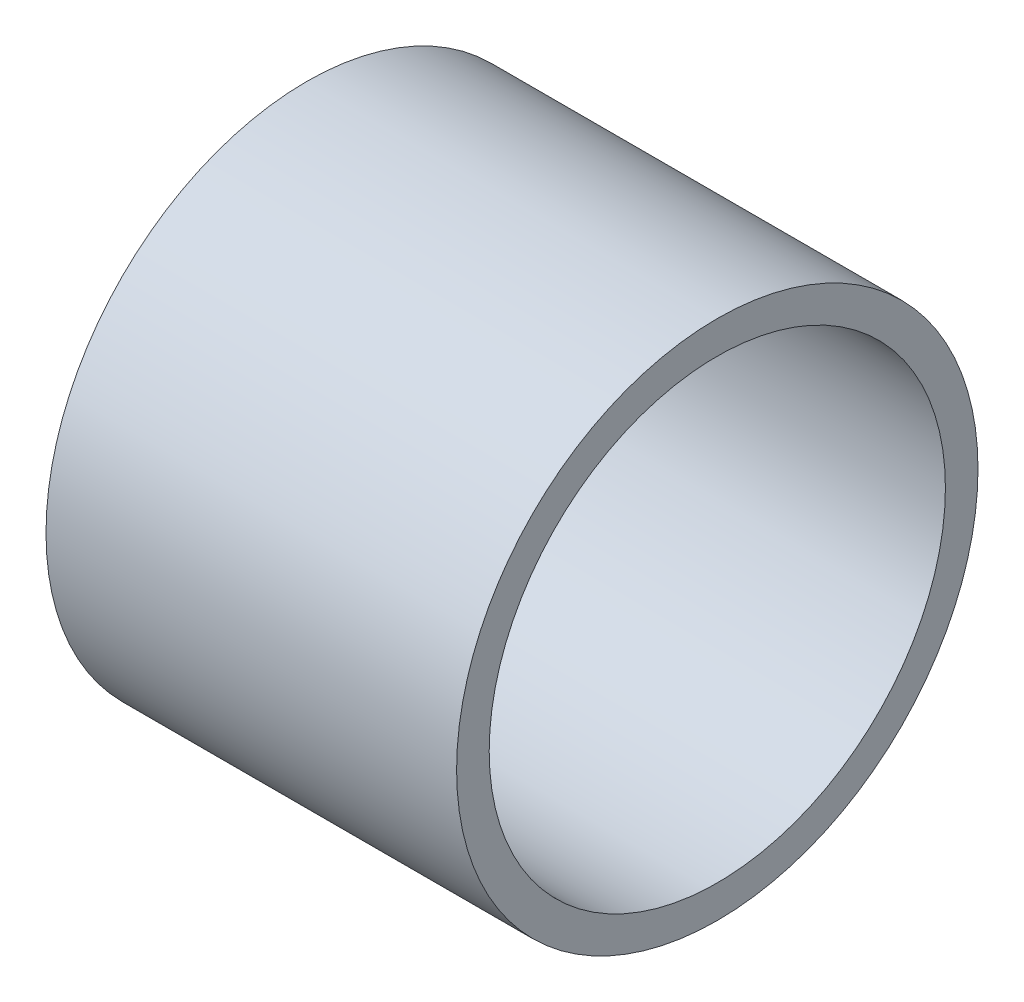
SolidWorks part; units mm, degrees
ref_plane "Front Plane" through (0, 0, 0) normal (0, 0, 1) x (1, 0, 0)
ref_plane "Top Plane" through (0, 0, 0) normal (0, 1, 0) x (1, 0, 0)
ref_plane "Right Plane" through (0, 0, 0) normal (1, 0, 0) x (0, 0, -1)
sketch "Sketch1" plane through (0, 0, 0) normal (1, 0, 0) x (0, 0, -1)
  circle A0 centre (0, 0) radius 8
  circle A1 centre (0, 0) radius 7
extrude "Boss-Extrude1" add sketch "Sketch1" along normal blind 6.3 and the other way blind 6.3
